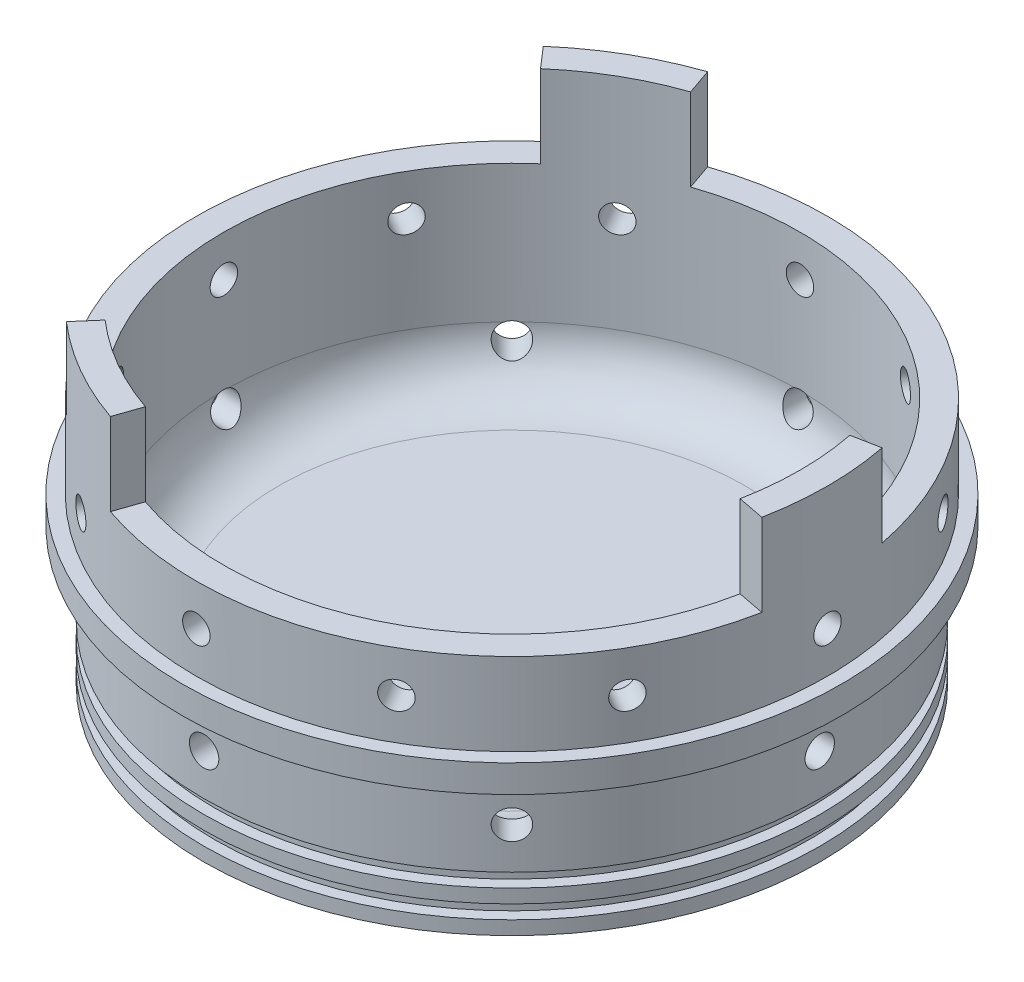
SolidWorks part; units mm, degrees
material "2024-T4"
ref_plane "Front Plane" through (0, 0, 0) normal (0, 0, 1) x (1, 0, 0)
ref_plane "Top Plane" through (0, 0, 0) normal (0, 1, 0) x (1, 0, 0)
ref_plane "Right Plane" through (0, 0, 0) normal (1, 0, 0) x (0, 0, -1)
sketch "Sketch1" plane through (0, 0, 0) normal (0, 1, 0) x (1, 0, 0)
  circle A0 centre (0, 0) radius 76.2
  dimension "D1" = 152.4
extrude "Center Ring(TotOD&Thk)" add sketch "Sketch1" along normal blind 6.35
sketch "Sketch2" plane through (0, 6.35, 0) normal (0, 1, 0) x (1, 0, 0)
  circle A0 centre (0, 0) radius 73.025
  dimension "D1" = 146.05
extrude "Top Ring(AcrylicID&Hgt)" add sketch "Sketch2" along normal blind 38.1
sketch "Sketch3" plane through (0, 0, 0) normal (0, -1, 0) x (1, 0, 0)
  circle A0 centre (0, 0) radius 71.247
  dimension "D1" = 142.494
extrude "Lower Ring(TankID&Depth)" add sketch "Sketch3" along normal blind 31.75
sketch "Sketch4" plane through (0, 44.45, 0) normal (0, 1, 0) x (1, 0, 0)
  circle A0 centre (0, 0) radius 66.675
  circle A1 centre (0, 0) radius 73.025 construction
  circle A2 centre (0, 0) radius 73.025
  dimension "D1" = 133.35
extrude "Bulkhead Hollow(UpperWall&BlkhdThk" cut sketch "Sketch4" against normal offset from surface (63.5 mm away) 12.7 contours A0 up to face at (0, -31.75, -71.247)
sketch "Sketch5" plane through (0, 0, 0) normal (0, 0, 1) x (1, 0, 0)
  line L0 (-71.247, 0) -> (-71.247, -31.75) construction
  line L1 (-71.247, 0) -> (-71.247, -31.75)
  line L2 (-71.247, -28.575) -> (-68.707, -28.575)
  line L3 (-68.707, -28.575) -> (-68.707, -25.4)
  line L4 (-68.707, -25.4) -> (-71.247, -25.4)
  line L5 (-71.247, -22.225) -> (-68.707, -22.225)
  line L6 (-68.707, -22.225) -> (-68.707, -19.05)
  line L7 (-68.707, -19.05) -> (-71.247, -19.05)
  line L8 (-71.247, -31.75) -> (71.247, -31.75) construction
  line L9 (0, 0) -> (0, -31.75) construction
  dimension "D1" = 2.54
  dimension "D2" = 3.175
  dimension "D3" = 3.175
  dimension "D4" = 3.175
  dimension "D5" = 3.175
revolve "O-Ring Channel" cut sketch "Sketch5" angle 360 about L9 region at (-69.977, -20.6375, 0) region at (-69.977, -26.9875, 0)
sketch "Sketch8" plane through (0, 0, 0) normal (0, 0, 1) x (1, 0, 0)
  circle A0 centre (0, -9.525) radius 3.4
  dimension "D1" = 6.8
  dimension "D2" = 9.525
extrude "Lower Bolt Hole (DrillDia&Dist)" cut sketch "Sketch8" along normal through all
pattern_circular "Lower Bolt Hole Ammount" count 8 over 360 about axis through (0, -31.75, 0) along (0, 1, 0) of "Lower Bolt Hole (DrillDia&Dist)" reverse direction yes
sketch "Sketch9" plane through (0, 0, 0) normal (0, 0, 1) x (1, 0, 0)
  line L0 (76.2, 6.35) -> (-76.2, 6.35) construction
  line L1 (76.2, 6.35) -> (-76.2, 6.35)
  circle A0 centre (0, 15.875) radius 3.175
  dimension "D1" = 6.35
  dimension "D2" = 9.525
extrude "Upper Bolt Hole (DrillDia&Dist)" cut sketch "Sketch9" against normal through all contours A0 region at (0, 15.875, 0)
pattern_circular "CirPattern1" count 12 over 360 about axis through (0, 44.45, 0) along (0, -1, 0) of "Upper Bolt Hole (DrillDia&Dist)"
fillet "Smoothing" radius 12.7 1 edges at (0, -19.05, -66.675)
sketch "Sketch10" plane through (0, 44.45, 0) normal (0, 1, 0) x (1, 0, 0)
  line L0 (65.4543, 12.7) -> (71.688, 13.9095)
  line L1 (65.4543, -12.7) -> (71.688, -13.9095)
  line L2 (-21.7286, -63.0351) -> (-23.798, -69.0384)
  line L3 (-43.7257, -50.3351) -> (-47.89, -55.1289)
  line L4 (-43.7257, 50.3351) -> (-47.89, 55.1289)
  line L5 (-21.7286, 63.0351) -> (-23.798, 69.0384)
  circle A0 centre (0, 0) radius 66.675 construction
  circle A1 centre (0, 0) radius 73.025
  circle A2 centre (0, 0) radius 73.025
  circle A3 centre (0, 0) radius 66.675
  point P20 (0, 0)
  circle M5 centre (0, 0) radius 66.675
  circle M6 centre (0, 0) radius 73.025
  dimension "D2" = 25.4
  dimension "D3" = 12.7
extrude "Cut-Extrude1" cut sketch "Sketch10" against normal blind 19.05 contours L5 L0 M5 M6 | L4 L3 M5 M6 | L2 L1 M5 M6 region at (33.9022, 44.45, -58.7204) region at (68.356, 44.45, 14.4135) region at (-67.8158, 44.45, 0)
equation "\"D4@Sketch5\"=\"D2@Sketch5\""
equation "\"D5@Sketch5\"=\"D3@Sketch5\""
equation "\"D3@Sketch10\"=\"D2@Sketch10\"/2"
